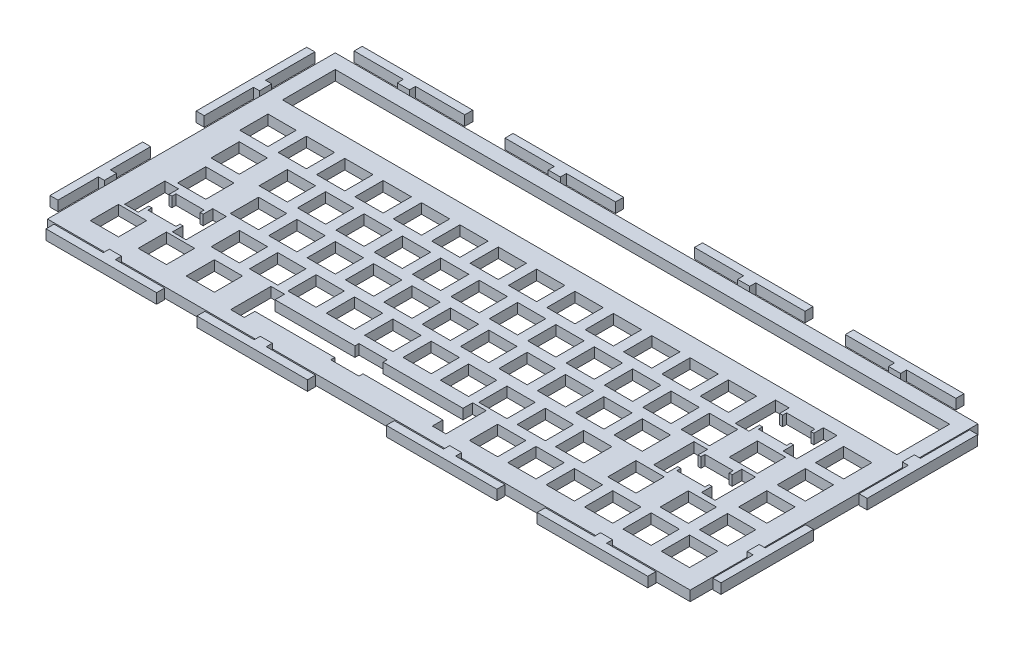
SolidWorks part; units mm, degrees
ref_plane "Front Plane" through (0, 0, 0) normal (0, 0, 1) x (1, 0, 0)
ref_plane "Top Plane" through (0, 0, 0) normal (0, 1, 0) x (1, 0, 0)
ref_plane "Right Plane" through (0, 0, 0) normal (1, 0, 0) x (0, 0, -1)
sketch "Sketch1" plane through (0, 0, 0) normal (0, 1, 0) x (1, 0, 0)
  line L2 (-75.7545, 37.9956) -> (-61.7545, 37.9956)
  line L3 (-94.8265, 37.9956) -> (-80.8265, 37.9956)
  line L4 (-94.8265, 37.9956) -> (-94.8265, 51.9956)
  line L5 (-94.8265, 51.9956) -> (-80.8265, 51.9956)
  line L6 (-80.8265, 37.9956) -> (-80.8265, 51.9956)
  line L7 (-75.7545, 37.9956) -> (-75.7545, 51.9956)
  line L8 (-75.7545, 51.9956) -> (-61.7545, 51.9956)
  line L9 (-61.7545, 37.9956) -> (-61.7545, 51.9956)
  line L10 (133.7495, 37.9956) -> (147.7495, 37.9956)
  line L11 (-37.6545, 37.9956) -> (-23.6545, 37.9956)
  line L12 (-56.7045, 37.9956) -> (-42.7045, 37.9956)
  line L13 (-56.7045, 37.9956) -> (-56.7045, 51.9956)
  line L14 (-56.7045, 51.9956) -> (-42.7045, 51.9956)
  line L15 (-42.7045, 37.9956) -> (-42.7045, 51.9956)
  line L16 (-37.6545, 37.9956) -> (-37.6545, 51.9956)
  line L17 (-37.6545, 51.9956) -> (-23.6545, 51.9956)
  line L18 (-23.6545, 37.9956) -> (-23.6545, 51.9956)
  line L19 (133.7495, 37.9956) -> (133.7495, 51.9956)
  line L20 (133.7495, 51.9956) -> (147.7495, 51.9956)
  line L21 (0.4455, 37.9956) -> (14.4455, 37.9956)
  line L22 (-18.6045, 37.9956) -> (-4.6045, 37.9956)
  line L23 (-18.6045, 37.9956) -> (-18.6045, 51.9956)
  line L24 (-18.6045, 51.9956) -> (-4.6045, 51.9956)
  line L25 (-4.6045, 37.9956) -> (-4.6045, 51.9956)
  line L26 (0.4455, 37.9956) -> (0.4455, 51.9956)
  line L27 (0.4455, 51.9956) -> (14.4455, 51.9956)
  line L28 (14.4455, 37.9956) -> (14.4455, 51.9956)
  line L29 (147.7495, 37.9956) -> (147.7495, 51.9956)
  line L30 (38.5455, 37.9956) -> (52.5455, 37.9956)
  line L31 (19.4955, 37.9956) -> (33.4955, 37.9956)
  line L32 (19.4955, 37.9956) -> (19.4955, 51.9956)
  line L33 (19.4955, 51.9956) -> (33.4955, 51.9956)
  line L34 (33.4955, 37.9956) -> (33.4955, 51.9956)
  line L35 (38.5455, 37.9956) -> (38.5455, 51.9956)
  line L36 (38.5455, 51.9956) -> (52.5455, 51.9956)
  line L37 (52.5455, 37.9956) -> (52.5455, 51.9956)
  line L38 (147.7495, 44.9956) -> (154.1495, 44.9956) construction
  line L39 (167.1835, 18.9456) -> (181.1835, 18.9456)
  line L40 (167.1835, 18.9456) -> (167.1835, 32.9456)
  line L41 (76.6455, 37.9956) -> (90.6455, 37.9956)
  line L42 (57.5955, 37.9956) -> (71.5955, 37.9956)
  line L43 (57.5955, 37.9956) -> (57.5955, 51.9956)
  line L44 (57.5955, 51.9956) -> (71.5955, 51.9956)
  line L45 (71.5955, 37.9956) -> (71.5955, 51.9956)
  line L46 (76.6455, 37.9956) -> (76.6455, 51.9956)
  line L47 (76.6455, 51.9956) -> (90.6455, 51.9956)
  line L48 (90.6455, 37.9956) -> (90.6455, 51.9956)
  line L49 (167.1835, 32.9456) -> (181.1835, 32.9456)
  line L50 (114.7225, 37.9956) -> (128.7225, 37.9956)
  line L51 (95.6955, 37.9956) -> (109.6955, 37.9956)
  line L52 (95.6955, 37.9956) -> (95.6955, 51.9956)
  line L53 (95.6955, 51.9956) -> (109.6955, 51.9956)
  line L54 (109.6955, 37.9956) -> (109.6955, 51.9956)
  line L55 (114.7225, 37.9956) -> (114.7225, 51.9956)
  line L56 (114.7225, 51.9956) -> (128.7225, 51.9956)
  line L57 (128.7225, 37.9956) -> (128.7225, 51.9956)
  line L58 (181.1835, 18.9456) -> (181.1835, 32.9456)
  line L59 (157.3735, 25.9456) -> (167.1835, 25.9456) construction
  line L73 (162.3995, 52.2456) -> (176.3995, 52.2456)
  line L75 (176.3995, 38.2456) -> (162.3995, 38.2456)
  line L77 (176.3995, 52.2456) -> (176.3995, 50.2456)
  line L78 (176.3995, 50.2456) -> (177.8995, 50.2456)
  line L79 (177.8995, 50.2456) -> (177.8995, 54.9956)
  line L80 (177.8995, 54.9956) -> (184.6495, 54.9956)
  line L81 (184.6495, 54.9956) -> (184.6495, 34.9956)
  line L82 (184.6495, 34.9956) -> (177.8995, 34.9956)
  line L83 (177.8995, 34.9956) -> (177.8995, 40.2456)
  line L84 (177.8995, 40.2456) -> (176.3995, 40.2456)
  line L85 (176.3995, 40.2456) -> (176.3995, 38.2456)
  line L86 (162.3995, 52.2456) -> (162.3995, 50.2456)
  line L87 (160.8995, 54.9956) -> (160.8995, 50.2456)
  line L88 (160.8995, 50.2456) -> (162.3995, 50.2456)
  line L89 (160.8995, 54.9956) -> (154.1495, 54.9956)
  line L90 (154.1495, 54.9956) -> (154.1495, 34.9956)
  line L91 (154.1495, 34.9956) -> (160.8995, 34.9956)
  line L92 (160.8995, 34.9956) -> (160.8995, 40.2456)
  line L93 (160.8995, 40.2456) -> (162.3995, 40.2456)
  line L94 (162.3995, 40.2456) -> (162.3995, 38.2456)
  line L116 (-47.1265, 18.9456) -> (-33.1265, 18.9456)
  line L117 (-66.1765, 18.9456) -> (-52.1765, 18.9456)
  line L118 (-66.1765, 18.9456) -> (-66.1765, 32.9456)
  line L119 (-66.1765, 32.9456) -> (-52.1765, 32.9456)
  line L120 (-52.1765, 18.9456) -> (-52.1765, 32.9456)
  line L121 (-47.1265, 18.9456) -> (-47.1265, 32.9456)
  line L122 (-47.1265, 32.9456) -> (-33.1265, 32.9456)
  line L123 (-33.1265, 18.9456) -> (-33.1265, 32.9456)
  line L125 (-9.0515, 18.9456) -> (4.9485, 18.9456)
  line L126 (-28.0765, 18.9456) -> (-14.0765, 18.9456)
  line L127 (-28.0765, 18.9456) -> (-28.0765, 32.9456)
  line L128 (-28.0765, 32.9456) -> (-14.0765, 32.9456)
  line L129 (-14.0765, 18.9456) -> (-14.0765, 32.9456)
  line L130 (-9.0515, 18.9456) -> (-9.0515, 32.9456)
  line L131 (-9.0515, 32.9456) -> (4.9485, 32.9456)
  line L132 (4.9485, 18.9456) -> (4.9485, 32.9456)
  line L135 (29.0735, 18.9456) -> (43.0735, 18.9456)
  line L136 (9.9485, 18.9456) -> (23.9485, 18.9456)
  line L137 (9.9485, 18.9456) -> (9.9485, 32.9456)
  line L138 (9.9485, 32.9456) -> (23.9485, 32.9456)
  line L139 (23.9485, 18.9456) -> (23.9485, 32.9456)
  line L140 (29.0735, 18.9456) -> (29.0735, 32.9456)
  line L141 (29.0735, 32.9456) -> (43.0735, 32.9456)
  line L142 (43.0735, 18.9456) -> (43.0735, 32.9456)
  line L144 (67.1485, 18.9456) -> (81.1485, 18.9456)
  line L145 (48.1235, 18.9456) -> (62.1235, 18.9456)
  line L146 (48.1235, 18.9456) -> (48.1235, 32.9456)
  line L147 (48.1235, 32.9456) -> (62.1235, 32.9456)
  line L148 (62.1235, 18.9456) -> (62.1235, 32.9456)
  line L149 (67.1485, 18.9456) -> (67.1485, 32.9456)
  line L150 (67.1485, 32.9456) -> (81.1485, 32.9456)
  line L151 (81.1485, 18.9456) -> (81.1485, 32.9456)
  line L152 (159.9865, 14.1456) -> (173.9865, 14.1456)
  line L153 (-42.3635, -0.1044) -> (-28.3635, -0.1044)
  line L154 (-61.4135, -0.1044) -> (-47.4135, -0.1044)
  line L155 (105.2735, 18.9456) -> (119.2735, 18.9456)
  line L156 (86.2235, 18.9456) -> (100.2235, 18.9456)
  line L157 (86.2235, 18.9456) -> (86.2235, 32.9456)
  line L158 (86.2235, 32.9456) -> (100.2235, 32.9456)
  line L159 (100.2235, 18.9456) -> (100.2235, 32.9456)
  line L160 (105.2735, 18.9456) -> (105.2735, 32.9456)
  line L161 (105.2735, 32.9456) -> (119.2735, 32.9456)
  line L162 (119.2735, 18.9456) -> (119.2735, 32.9456)
  line L163 (-61.4135, -0.1044) -> (-61.4135, 13.8956)
  line L172 (-94.8265, 37.9956) -> (-94.8265, 32.9456) construction
  line L173 (-61.4135, 13.8956) -> (-47.4135, 13.8956)
  line L174 (-47.4135, -0.1044) -> (-47.4135, 13.8956)
  line L175 (-90.0635, 18.9456) -> (-76.0635, 18.9456)
  line L176 (-90.0635, 18.9456) -> (-90.0635, 32.9456)
  line L177 (-90.0635, 32.9456) -> (-76.0635, 32.9456)
  line L178 (-76.0635, 18.9456) -> (-76.0635, 32.9456)
  line L179 (-94.8265, 32.9456) -> (-90.0635, 32.9456) construction
  line L180 (124.3235, 18.9456) -> (138.3235, 18.9456)
  line L185 (124.3235, 18.9456) -> (124.3235, 32.9456)
  line L186 (124.3235, 32.9456) -> (138.3235, 32.9456)
  line L187 (138.3235, 18.9456) -> (138.3235, 32.9456)
  line L188 (-42.3635, -0.1044) -> (-42.3635, 13.8956)
  line L189 (143.3735, 18.9456) -> (157.3735, 18.9456)
  line L190 (143.3735, 18.9456) -> (143.3735, 32.9456)
  line L191 (143.3735, 32.9456) -> (157.3735, 32.9456)
  line L192 (157.3735, 18.9456) -> (157.3735, 32.9456)
  line L193 (-42.3635, 13.8956) -> (-28.3635, 13.8956)
  line L194 (-28.3635, -0.1044) -> (-28.3635, 13.8956)
  line L195 (-4.2635, -0.1044) -> (9.7365, -0.1044)
  line L196 (-23.3135, -0.1044) -> (-9.3135, -0.1044)
  line L197 (-23.3135, -0.1044) -> (-23.3135, 13.8956)
  line L198 (-23.3135, 13.8956) -> (-9.3135, 13.8956)
  line L199 (-9.3135, -0.1044) -> (-9.3135, 13.8956)
  line L200 (-4.2635, -0.1044) -> (-4.2635, 13.8956)
  line L201 (-4.2635, 13.8956) -> (9.7365, 13.8956)
  line L202 (9.7365, -0.1044) -> (9.7365, 13.8956)
  line L203 (33.8365, -0.1044) -> (47.8365, -0.1044)
  line L204 (14.7865, -0.1044) -> (28.7865, -0.1044)
  line L205 (14.7865, -0.1044) -> (14.7865, 13.8956)
  line L206 (14.7865, 13.8956) -> (28.7865, 13.8956)
  line L207 (28.7865, -0.1044) -> (28.7865, 13.8956)
  line L208 (33.8365, -0.1044) -> (33.8365, 13.8956)
  line L209 (33.8365, 13.8956) -> (47.8365, 13.8956)
  line L210 (47.8365, -0.1044) -> (47.8365, 13.8956)
  line L211 (71.9365, -0.1044) -> (85.9365, -0.1044)
  line L212 (52.8865, -0.1044) -> (66.8865, -0.1044)
  line L213 (52.8865, -0.1044) -> (52.8865, 13.8956)
  line L214 (52.8865, 13.8956) -> (66.8865, 13.8956)
  line L215 (66.8865, -0.1044) -> (66.8865, 13.8956)
  line L216 (71.9365, -0.1044) -> (71.9365, 13.8956)
  line L217 (71.9365, 13.8956) -> (85.9365, 13.8956)
  line L218 (85.9365, -0.1044) -> (85.9365, 13.8956)
  line L219 (110.0365, -0.1044) -> (124.0365, -0.1044)
  line L220 (90.9865, -0.1044) -> (104.9865, -0.1044)
  line L221 (90.9865, -0.1044) -> (90.9865, 13.8956)
  line L222 (90.9865, 13.8956) -> (104.9865, 13.8956)
  line L223 (104.9865, -0.1044) -> (104.9865, 13.8956)
  line L224 (110.0365, -0.1044) -> (110.0365, 13.8956)
  line L225 (110.0365, 13.8956) -> (124.0365, 13.8956)
  line L226 (124.0365, -0.1044) -> (124.0365, 13.8956)
  line L227 (-87.6075, -0.1044) -> (-73.6075, -0.1044)
  line L228 (-87.6075, -0.1044) -> (-87.6075, 13.8956)
  line L229 (-87.6075, 13.8956) -> (-73.6075, 13.8956)
  line L230 (-73.6075, -0.1044) -> (-73.6075, 13.8956)
  line L231 (-90.0635, 18.9456) -> (-90.0635, 13.8956) construction
  line L232 (129.0865, -0.1044) -> (143.0865, -0.1044)
  line L233 (129.0865, -0.1044) -> (129.0865, 13.8956)
  line L234 (129.0865, 13.8956) -> (143.0865, 13.8956)
  line L235 (143.0865, -0.1044) -> (143.0865, 13.8956)
  line L240 (-90.0635, 13.8956) -> (-87.6075, 13.8956) construction
  line L241 (173.9865, 0.1456) -> (159.9865, 0.1456)
  line L242 (173.9865, 14.1456) -> (173.9865, 12.1456)
  line L243 (173.9865, 12.1456) -> (175.4865, 12.1456)
  line L244 (175.4865, 12.1456) -> (175.4865, 16.8956)
  line L245 (175.4865, 16.8956) -> (182.2365, 16.8956)
  line L246 (182.2365, 16.8956) -> (182.2365, -3.1044)
  line L247 (182.2365, -3.1044) -> (175.4865, -3.1044)
  line L248 (175.4865, -3.1044) -> (175.4865, 2.1456)
  line L249 (175.4865, 2.1456) -> (173.9865, 2.1456)
  line L250 (173.9865, 2.1456) -> (173.9865, 0.1456)
  line L251 (159.9865, 14.1456) -> (159.9865, 12.1456)
  line L252 (158.4865, 16.8956) -> (158.4865, 12.1456)
  line L253 (158.4865, 12.1456) -> (159.9865, 12.1456)
  line L254 (158.4865, 16.8956) -> (151.7365, 16.8956)
  line L255 (151.7365, 16.8956) -> (151.7365, -3.1044)
  line L256 (151.7365, -3.1044) -> (158.4865, -3.1044)
  line L257 (158.4865, -3.1044) -> (158.4865, 2.1456)
  line L258 (158.4865, 2.1456) -> (159.9865, 2.1456)
  line L259 (159.9865, 2.1456) -> (159.9865, 0.1456)
  line L260 (143.0865, 12.1456) -> (151.7365, 12.1456) construction
  line L262 (-32.8385, -19.1544) -> (-18.8385, -19.1544)
  line L263 (-51.8885, -19.1544) -> (-37.8885, -19.1544)
  line L264 (-51.8885, -19.1544) -> (-51.8885, -5.1544)
  line L265 (-51.8885, -5.1544) -> (-37.8885, -5.1544)
  line L266 (-37.8885, -19.1544) -> (-37.8885, -5.1544)
  line L267 (-32.8385, -19.1544) -> (-32.8385, -5.1544)
  line L268 (-32.8385, -5.1544) -> (-18.8385, -5.1544)
  line L269 (-18.8385, -19.1544) -> (-18.8385, -5.1544)
  line L270 (5.2615, -19.1544) -> (19.2615, -19.1544)
  line L271 (-13.7885, -19.1544) -> (0.2115, -19.1544)
  line L272 (-13.7885, -19.1544) -> (-13.7885, -5.1544)
  line L273 (-13.7885, -5.1544) -> (0.2115, -5.1544)
  line L274 (0.2115, -19.1544) -> (0.2115, -5.1544)
  line L275 (5.2615, -19.1544) -> (5.2615, -5.1544)
  line L276 (5.2615, -5.1544) -> (19.2615, -5.1544)
  line L277 (19.2615, -19.1544) -> (19.2615, -5.1544)
  line L278 (43.3615, -19.1544) -> (57.3615, -19.1544)
  line L279 (24.3115, -19.1544) -> (38.3115, -19.1544)
  line L280 (24.3115, -19.1544) -> (24.3115, -5.1544)
  line L281 (24.3115, -5.1544) -> (38.3115, -5.1544)
  line L282 (38.3115, -19.1544) -> (38.3115, -5.1544)
  line L283 (43.3615, -19.1544) -> (43.3615, -5.1544)
  line L284 (43.3615, -5.1544) -> (57.3615, -5.1544)
  line L285 (57.3615, -19.1544) -> (57.3615, -5.1544)
  line L286 (81.4615, -19.6544) -> (95.4615, -19.6544)
  line L287 (62.4115, -19.6544) -> (76.4115, -19.6544)
  line L288 (62.4115, -19.6544) -> (62.4115, -5.6544)
  line L289 (62.4115, -5.6544) -> (76.4115, -5.6544)
  line L290 (76.4115, -19.6544) -> (76.4115, -5.6544)
  line L291 (81.4615, -19.6544) -> (81.4615, -5.6544)
  line L292 (81.4615, -5.6544) -> (95.4615, -5.6544)
  line L293 (95.4615, -19.6544) -> (95.4615, -5.6544)
  line L294 (119.5615, -19.6544) -> (133.5615, -19.6544)
  line L295 (100.5115, -19.6544) -> (114.5115, -19.6544)
  line L296 (100.5115, -19.6544) -> (100.5115, -5.6544)
  line L297 (100.5115, -5.6544) -> (114.5115, -5.6544)
  line L298 (114.5115, -19.6544) -> (114.5115, -5.6544)
  line L299 (119.5615, -19.6544) -> (119.5615, -5.6544)
  line L300 (119.5615, -5.6544) -> (133.5615, -5.6544)
  line L301 (133.5615, -19.6544) -> (133.5615, -5.6544)
  line L306 (-83.3445, -5.1544) -> (-69.3445, -5.1544)
  line L307 (145.5235, -19.6544) -> (159.5235, -19.6544)
  line L308 (145.5235, -19.6544) -> (145.5235, -5.6544)
  line L309 (145.5235, -5.6544) -> (159.5235, -5.6544)
  line L310 (159.5235, -19.6544) -> (159.5235, -5.6544)
  line L311 (-69.3445, -19.1544) -> (-83.3445, -19.1544)
  line L331 (171.4855, -19.6544) -> (185.4855, -19.6544)
  line L332 (171.4855, -19.6544) -> (171.4855, -5.6544)
  line L333 (171.4855, -5.6544) -> (185.4855, -5.6544)
  line L334 (185.4855, -19.6544) -> (185.4855, -5.6544)
  line L335 (159.5235, -12.6544) -> (171.4855, -12.6544) construction
  line L336 (-61.4135, -0.1044) -> (-61.4135, -5.1544) construction
  line L337 (-61.4135, -5.1544) -> (-51.8885, -5.1544) construction
  line L338 (-104.4215, 94.9896) -> (-117.5239, 94.9896) construction
  line L339 (-97.2765, 61.6456) -> (207.7235, 61.6456)
  line L340 (190.9955, 18.9456) -> (204.9955, 18.9456)
  line L341 (190.9955, 18.9456) -> (190.9955, 32.9456)
  line L342 (190.9955, 32.9456) -> (204.9955, 32.9456)
  line L343 (204.9955, 18.9456) -> (204.9955, 32.9456)
  line L344 (181.1835, 25.9456) -> (190.9955, 25.9456) construction
  line L345 (190.9745, 37.9956) -> (204.9745, 37.9956)
  line L346 (190.9745, 37.9956) -> (190.9745, 51.9956)
  line L347 (190.9745, 51.9956) -> (204.9745, 51.9956)
  line L348 (204.9745, 37.9956) -> (204.9745, 51.9956)
  line L349 (184.6495, 44.9956) -> (190.9745, 44.9956) construction
  line L350 (190.9425, -0.1044) -> (204.9425, -0.1044)
  line L351 (190.9425, -0.1044) -> (190.9425, 13.8956)
  line L352 (190.9425, 13.8956) -> (204.9425, 13.8956)
  line L353 (204.9425, -0.1044) -> (204.9425, 13.8956)
  line L354 (182.2365, 6.8956) -> (190.9425, 6.8956) construction
  line L355 (190.9855, -19.6544) -> (204.9855, -19.6544)
  line L356 (190.9855, -19.6544) -> (190.9855, -5.6544)
  line L357 (190.9855, -5.6544) -> (204.9855, -5.6544)
  line L358 (204.9855, -19.6544) -> (204.9855, -5.6544)
  line L359 (185.4855, -12.6544) -> (190.9855, -12.6544) construction
  line L360 (-69.3445, -5.1544) -> (-69.3445, -7.1544)
  line L361 (-69.3445, -7.1544) -> (-67.8445, -7.1544)
  line L362 (-67.8445, -7.1544) -> (-67.8445, -2.4044)
  line L363 (-67.8445, -2.4044) -> (-61.0945, -2.4044)
  line L364 (-61.0945, -2.4044) -> (-61.0945, -22.4044)
  line L365 (-61.0945, -22.4044) -> (-67.8445, -22.4044)
  line L366 (-67.8445, -22.4044) -> (-67.8445, -17.1544)
  line L367 (-67.8445, -17.1544) -> (-69.3445, -17.1544)
  line L368 (-69.3445, -17.1544) -> (-69.3445, -19.1544)
  line L369 (-83.3445, -5.1544) -> (-83.3445, -7.1544)
  line L370 (-84.8445, -2.4044) -> (-84.8445, -7.1544)
  line L371 (-84.8445, -7.1544) -> (-83.3445, -7.1544)
  line L372 (-84.8445, -2.4044) -> (-91.5945, -2.4044)
  line L373 (-91.5945, -2.4044) -> (-91.5945, -22.4044)
  line L374 (-91.5945, -22.4044) -> (-84.8445, -22.4044)
  line L375 (-84.8445, -22.4044) -> (-84.8445, -17.1544)
  line L376 (-84.8445, -17.1544) -> (-83.3445, -17.1544)
  line L377 (-83.3445, -17.1544) -> (-83.3445, -19.1544)
  line L378 (-93.0945, -37.9544) -> (-79.0945, -37.9544)
  line L379 (-93.0945, -37.9544) -> (-93.0945, -23.9544)
  line L380 (-93.0945, -23.9544) -> (-79.0945, -23.9544)
  line L381 (-79.0945, -37.9544) -> (-79.0945, -23.9544)
  line L382 (-69.2945, -37.9544) -> (-55.2945, -37.9544)
  line L383 (-69.2945, -37.9544) -> (-69.2945, -23.9544)
  line L384 (-69.2945, -23.9544) -> (-55.2945, -23.9544)
  line L385 (-55.2945, -37.9544) -> (-55.2945, -23.9544)
  line L390 (-45.4945, -37.9544) -> (-31.4945, -37.9544)
  line L391 (-45.4945, -37.9544) -> (-45.4945, -23.9544)
  line L392 (-45.4945, -23.9544) -> (-31.4945, -23.9544)
  line L393 (-31.4945, -37.9544) -> (-31.4945, -23.9544)
  line L394 (-55.2945, -23.9544) -> (-45.4945, -23.9544) construction
  line L395 (26.4395, -24.1144) -> (40.4395, -24.1144)
  line L396 (40.4395, -38.1144) -> (26.4395, -38.1144)
  line L397 (40.4395, -24.1144) -> (40.4395, -26.1144)
  line L398 (40.4395, -26.1144) -> (80.1235, -26.1144)
  line L399 (80.1235, -26.1144) -> (80.1235, -21.3644)
  line L400 (80.1235, -21.3644) -> (86.8735, -21.3644)
  line L401 (86.8735, -21.3644) -> (86.8735, -41.3644)
  line L402 (86.8735, -41.3644) -> (80.1235, -41.3644)
  line L403 (80.1235, -41.3644) -> (80.1235, -36.1144)
  line L404 (80.1235, -36.1144) -> (40.4395, -36.1144)
  line L405 (40.4395, -36.1144) -> (40.4395, -38.1144)
  line L406 (26.4395, -24.1144) -> (26.4395, -26.1144)
  line L407 (-13.2445, -21.3644) -> (-13.2445, -26.1144)
  line L408 (-13.2445, -26.1144) -> (26.4395, -26.1144)
  line L409 (-13.2445, -21.3644) -> (-19.9945, -21.3644)
  line L410 (-19.9945, -21.3644) -> (-19.9945, -41.3644)
  line L411 (-19.9945, -41.3644) -> (-13.2445, -41.3644)
  line L412 (-13.2445, -41.3644) -> (-13.2445, -36.1144)
  line L413 (-13.2445, -36.1144) -> (26.4395, -36.1144)
  line L414 (26.4395, -36.1144) -> (26.4395, -38.1144)
  line L415 (95.5435, -38.3644) -> (109.5435, -38.3644)
  line L416 (95.5435, -38.3644) -> (95.5435, -24.3644)
  line L417 (95.5435, -24.3644) -> (109.5435, -24.3644)
  line L418 (109.5435, -38.3644) -> (109.5435, -24.3644)
  line L419 (86.8735, -31.3644) -> (95.5435, -31.3644) construction
  line L420 (114.5935, -38.3644) -> (128.5935, -38.3644)
  line L421 (114.5935, -38.3644) -> (114.5935, -24.3644)
  line L422 (114.5935, -24.3644) -> (128.5935, -24.3644)
  line L423 (128.5935, -38.3644) -> (128.5935, -24.3644)
  line L424 (114.5935, -31.3644) -> (109.5435, -31.3644) construction
  line L425 (133.6435, -38.3644) -> (147.6435, -38.3644)
  line L426 (133.6435, -38.3644) -> (133.6435, -24.3644)
  line L427 (133.6435, -24.3644) -> (147.6435, -24.3644)
  line L428 (147.6435, -38.3644) -> (147.6435, -24.3644)
  line L429 (152.6935, -38.3644) -> (166.6935, -38.3644)
  line L430 (152.6935, -38.3644) -> (152.6935, -24.3644)
  line L431 (152.6935, -24.3644) -> (166.6935, -24.3644)
  line L432 (166.6935, -38.3644) -> (166.6935, -24.3644)
  line L433 (171.7435, -38.3644) -> (185.7435, -38.3644)
  line L434 (171.7435, -38.3644) -> (171.7435, -24.3644)
  line L435 (171.7435, -24.3644) -> (185.7435, -24.3644)
  line L436 (185.7435, -38.3644) -> (185.7435, -24.3644)
  line L437 (190.7935, -38.3644) -> (204.7935, -38.3644)
  line L438 (190.7935, -38.3644) -> (190.7935, -24.3644)
  line L439 (190.7935, -24.3644) -> (204.7935, -24.3644)
  line L440 (204.7935, -38.3644) -> (204.7935, -24.3644)
  line L441 (-97.2765, 61.6456) -> (-97.2765, 87.8456)
  line L442 (-97.2765, 87.8456) -> (207.7235, 87.8456)
  line L443 (207.7235, 61.6456) -> (207.7235, 87.8456)
  line L444 (-104.4215, 94.9896) -> (214.6585, 94.9896)
  line L445 (-104.4215, 94.9896) -> (-104.4215, -47.8854)
  line L446 (-104.4215, -47.8854) -> (214.6585, -47.8854)
  line L447 (214.6585, 94.9896) -> (214.6585, -47.8854)
  line L448 (-117.5239, 94.9896) -> (-117.5239, 25.8096) construction
  line L449 (-104.4215, -47.8854) -> (-117.5239, -47.8854) construction
  line L450 (-117.5239, -47.8854) -> (-117.5239, 14.6046) construction
  line L451 (-150.5498, 25.8096) -> (-98.6233, 25.8096) construction
  line L452 (-150.5498, 14.6046) -> (-97.2765, 14.6046) construction
  line L453 (-104.4215, 94.9896) -> (-104.4215, 60.3996) construction
  point P115 (128.7225, 44.9956)
  point P116 (154.1495, 44.9956)
  dimension "D1" = 14
  dimension "D2" = 20
  dimension "D3" = 4.75
  dimension "D4" = 6.75
  dimension "D5" = 1.5
  dimension "D6" = 2
  dimension "D13" = 14
  dimension "D14" = 14
  dimension "D15" = 5.072
  dimension "D16" = 14
  dimension "D17" = 5.05
  dimension "D18" = 5.05
  dimension "D19" = 14
  dimension "D20" = 4.763
  dimension "D21" = 5.05
  dimension "D22" = 9.887
  dimension "D23" = 26.2
  dimension "D24" = 14
  dimension "D25" = 14
  dimension "D26" = 5.05
  dimension "D27" = 5.05
  dimension "D28" = 5.05
  dimension "D29" = 5.05
  dimension "D30" = 5.05
  dimension "D31" = 5.05
  dimension "D32" = 5.05
  dimension "D33" = 5.05
  dimension "D34" = 5.05
  dimension "D35" = 5.027
  dimension "D36" = 5.05
  dimension "D37" = 5.05
  dimension "D38" = 5.025
  dimension "D39" = 5
  dimension "D40" = 5.125
  dimension "D41" = 5.05
  dimension "D42" = 5.025
  dimension "D43" = 5.075
  dimension "D44" = 5.05
  dimension "D45" = 5.05
  dimension "D46" = 5.027
  dimension "D47" = 14.65
  dimension "D48" = 14
  dimension "D49" = 9.81
  dimension "D50" = 12.194
  dimension "D51" = 5.05
  dimension "D52" = 5.05
  dimension "D53" = 5.05
  dimension "D54" = 5.05
  dimension "D55" = 5.05
  dimension "D56" = 5.05
  dimension "D57" = 5.05
  dimension "D58" = 5.05
  dimension "D59" = 5.05
  dimension "D60" = 5.05
  dimension "D61" = 14
  dimension "D62" = 20
  dimension "D63" = 5.05
  dimension "D64" = 2.456
  dimension "D65" = 4.75
  dimension "D66" = 6.75
  dimension "D67" = 1.5
  dimension "D68" = 2
  dimension "D69" = 16.9
  dimension "D70" = 14
  dimension "D71" = 5.05
  dimension "D72" = 5.05
  dimension "D73" = 5.05
  dimension "D74" = 5.05
  dimension "D75" = 5.05
  dimension "D76" = 5.05
  dimension "D77" = 5.05
  dimension "D78" = 5.05
  dimension "D79" = 5.05
  dimension "D80" = 11.962
  dimension "D81" = 20
  dimension "D82" = 14
  dimension "D83" = 11.962
  dimension "D84" = 14
  dimension "D85" = 14
  dimension "D86" = 9.812
  dimension "D87" = 14
  dimension "D88" = 14.575
  dimension "D89" = 4.75
  dimension "D90" = 14
  dimension "D91" = 6.75
  dimension "D92" = 14
  dimension "D93" = 16.956
  dimension "D94" = 14
  dimension "D95" = 5.5
  dimension "D96" = 5.05
  dimension "D97" = 5.05
  dimension "D98" = 9.525
  dimension "D99" = 1.5
  dimension "D100" = 2
  dimension "D101" = 5.05
  dimension "D102" = 9.206
  dimension "D103" = 5.05
  dimension "D104" = 14
  dimension "D105" = 14
  dimension "D106" = 14
  dimension "D107" = 14
  dimension "D108" = 1.5
  dimension "D109" = 9.8
  dimension "D110" = 5.05
  dimension "D111" = 9.8
  dimension "D112" = 5.05
  dimension "D113" = 5.05
  dimension "D114" = 14
  dimension "D115" = 14
  dimension "D116" = 20
  dimension "D117" = 4.75
  dimension "D118" = 6.75
  dimension "D119" = 39.684
  dimension "D120" = 2
  dimension "D121" = 5.05
  dimension "D122" = 11.5
  dimension "D123" = 14
  dimension "D124" = 8.67
  dimension "D125" = 5.25
  dimension "D126" = 14
  dimension "D127" = 5.05
  dimension "D128" = 14
  dimension "D129" = 14
  dimension "D130" = 14
  dimension "D131" = 14
  dimension "D132" = 5.05
  dimension "D133" = 5.05
  dimension "D134" = 5.05
  dimension "D135" = 5.05
  dimension "D136" = 4.8
  dimension "D137" = 5.25
  dimension "D138" = 5.25
  dimension "D139" = 5.25
  dimension "D140" = 305
  dimension "D141" = 9.65
  dimension "D142" = 142.875
  dimension "D143" = 319.08
  dimension "D144" = 7.144
  dimension "D145" = 7.145
  dimension "D146" = 2.45
  dimension "D147" = 69.18
  dimension "D148" = 62.49
extrude "Boss-Extrude2" add sketch "Sketch1" along normal mid plane 5
sketch "Sketch2" plane through (0, 2.5, 0) normal (0, 1, 0) x (1, 0, 0)
  line L0 (-104.4215, 25.7896) -> (-104.4215, 14.6146) construction
  line L1 (-104.4215, -47.8854) -> (-104.4215, 14.6146) construction
  line L2 (-104.4215, 94.9896) -> (-104.4215, -47.8854) construction
  line L3 (-104.4215, 94.9896) -> (-104.4215, 25.7896) construction
  line L4 (-104.4215, 60.3896) -> (-192.4203, 60.3896) construction
  line L5 (-104.4215, 63.3896) -> (-104.4215, 57.3896)
  line L6 (-104.4215, 63.3896) -> (-107.4215, 63.3896)
  line L7 (-104.4215, 57.3896) -> (-107.4215, 57.3896)
  line L8 (-107.4215, 63.3896) -> (-107.4215, 87.8456)
  line L9 (-107.4215, 57.3896) -> (-107.4215, 32.9456)
  line L10 (-107.4215, 87.8456) -> (-111.4215, 87.8456)
  line L11 (-111.4215, 87.8456) -> (-111.4215, 32.9456)
  line L12 (-111.4215, 32.9456) -> (-107.4215, 32.9456)
  line L13 (207.7235, 87.8456) -> (-97.2765, 87.8456) construction
  line L14 (-107.4215, 20.2021) -> (-104.4215, 20.2021) construction
  line L15 (-76.0635, 32.9456) -> (-90.0635, 32.9456) construction
  line L16 (-107.4215, 31.2421) -> (-107.4215, 9.1621) construction
  line L17 (-104.4215, -13.6354) -> (-104.4215, -19.6354)
  line L18 (-104.4215, -13.6354) -> (-107.4215, -13.6354)
  line L19 (-104.4215, -19.6354) -> (-107.4215, -19.6354)
  line L20 (-107.4215, -13.6354) -> (-107.4215, 6.3646)
  line L21 (-107.4215, 6.3646) -> (-111.4215, 6.3646)
  line L22 (-111.4215, 6.3646) -> (-111.4215, -39.6354)
  line L23 (-111.4215, -39.6354) -> (-107.4215, -39.6354)
  line L24 (-107.4215, -39.6354) -> (-107.4215, -19.6354)
  line L25 (214.6585, 14.5646) -> (214.6585, -47.8854) construction
  line L26 (55.1185, 125.0696) -> (55.1185, -78.0627) construction
  line L27 (221.6585, -39.6354) -> (217.6585, -39.6354)
  line L28 (221.6585, 6.3646) -> (221.6585, -39.6354)
  line L29 (217.6585, 6.3646) -> (221.6585, 6.3646)
  line L30 (217.6585, -13.6354) -> (217.6585, 6.3646)
  line L31 (214.6585, -13.6354) -> (217.6585, -13.6354)
  line L32 (214.6585, -13.6354) -> (214.6585, -19.6354)
  line L33 (214.6585, -19.6354) -> (217.6585, -19.6354)
  line L34 (217.6585, -39.6354) -> (217.6585, -19.6354)
  line L35 (214.6585, 63.3896) -> (217.6585, 63.3896)
  line L36 (217.6585, 63.3896) -> (217.6585, 87.8456)
  line L37 (217.6585, 87.8456) -> (221.6585, 87.8456)
  line L38 (221.6585, 87.8456) -> (221.6585, 32.9456)
  line L39 (221.6585, 32.9456) -> (217.6585, 32.9456)
  line L40 (217.6585, 57.3896) -> (217.6585, 32.9456)
  line L41 (214.6585, 57.3896) -> (217.6585, 57.3896)
  line L42 (214.6585, 63.3896) -> (214.6585, 57.3896)
  line L43 (214.6585, -47.8854) -> (214.6585, 94.9896) construction
  line L44 (214.6585, 94.9896) -> (214.6585, 25.7896) construction
  line L45 (214.6585, 25.7896) -> (214.6585, 14.5646) construction
  line L46 (214.6585, 20.1771) -> (217.6585, 20.1771) construction
  line L47 (217.6585, 31.2421) -> (217.6585, 9.1621) construction
  line L48 (55.1185, 94.9896) -> (55.1185, -47.8854) construction
  line L49 (214.6585, 94.9896) -> (-104.4215, 94.9896) construction
  line L50 (-104.4215, -47.8854) -> (214.6585, -47.8854) construction
  line L51 (55.1185, 23.5034) -> (270.1989, 23.5034) construction
  line L52 (55.1185, 23.5034) -> (-168.679, 23.5034) construction
  line L53 (214.6585, 94.9896) -> (56.9085, 94.9896) construction
  line L54 (-104.4215, 94.9896) -> (45.7235, 94.9896) construction
  line L55 (45.7235, 94.9896) -> (56.9085, 94.9896) construction
  line L56 (51.316, 94.9896) -> (51.316, 98.9896) construction
  line L57 (40.276, 98.9896) -> (62.356, 98.9896) construction
  line L58 (170.2335, 94.9896) -> (176.2335, 94.9896)
  line L59 (176.2335, 94.9896) -> (176.2335, 97.9896)
  line L60 (176.2335, 97.9896) -> (200.6835, 97.9896)
  line L61 (200.6835, 97.9896) -> (200.6835, 101.9896)
  line L62 (200.6835, 101.9896) -> (145.7835, 101.9896)
  line L63 (145.7835, 101.9896) -> (145.7835, 97.9896)
  line L64 (145.7835, 97.9896) -> (170.2335, 97.9896)
  line L65 (170.2335, 97.9896) -> (170.2335, 94.9896)
  line L66 (95.3335, 94.9896) -> (101.3335, 94.9896)
  line L67 (101.3335, 94.9896) -> (101.3335, 97.9896)
  line L68 (101.3335, 97.9896) -> (125.7835, 97.9896)
  line L69 (125.7835, 97.9896) -> (125.7835, 101.9896)
  line L70 (125.7835, 101.9896) -> (70.8835, 101.9896)
  line L71 (70.8835, 101.9896) -> (70.8835, 97.9896)
  line L72 (70.8835, 97.9896) -> (95.3335, 97.9896)
  line L73 (95.3335, 97.9896) -> (95.3335, 94.9896)
  line L74 (125.7835, 99.9896) -> (145.7835, 99.9896) construction
  line L75 (135.7835, 94.9896) -> (135.7835, 104.9896) construction
  line L76 (-43.1515, 97.9896) -> (-67.6015, 97.9896)
  line L77 (-43.1515, 101.9896) -> (-43.1515, 97.9896)
  line L78 (-98.0515, 101.9896) -> (-43.1515, 101.9896)
  line L79 (-98.0515, 97.9896) -> (-98.0515, 101.9896)
  line L80 (-73.6015, 97.9896) -> (-98.0515, 97.9896)
  line L81 (-73.6015, 94.9896) -> (-73.6015, 97.9896)
  line L82 (-67.6015, 94.9896) -> (-73.6015, 94.9896)
  line L83 (-67.6015, 97.9896) -> (-67.6015, 94.9896)
  line L84 (7.2985, 97.9896) -> (7.2985, 94.9896)
  line L85 (31.7485, 97.9896) -> (7.2985, 97.9896)
  line L86 (31.7485, 101.9896) -> (31.7485, 97.9896)
  line L87 (-23.1515, 101.9896) -> (31.7485, 101.9896)
  line L88 (-23.1515, 97.9896) -> (-23.1515, 101.9896)
  line L89 (1.2985, 97.9896) -> (-23.1515, 97.9896)
  line L90 (1.2985, 94.9896) -> (1.2985, 97.9896)
  line L91 (7.2985, 94.9896) -> (1.2985, 94.9896)
  line L92 (145.7835, -50.9827) -> (170.2335, -50.9827)
  line L93 (145.7835, -54.9827) -> (145.7835, -50.9827)
  line L94 (200.6835, -54.9827) -> (145.7835, -54.9827)
  line L95 (200.6835, -50.9827) -> (200.6835, -54.9827)
  line L96 (176.2335, -50.9827) -> (200.6835, -50.9827)
  line L97 (176.2335, -47.9827) -> (176.2335, -50.9827)
  line L98 (170.2335, -47.9827) -> (176.2335, -47.9827)
  line L99 (170.2335, -50.9827) -> (170.2335, -47.9827)
  line L100 (95.3335, -50.9827) -> (95.3335, -47.9827)
  line L101 (70.8835, -50.9827) -> (95.3335, -50.9827)
  line L102 (70.8835, -54.9827) -> (70.8835, -50.9827)
  line L103 (125.7835, -54.9827) -> (70.8835, -54.9827)
  line L104 (125.7835, -50.9827) -> (125.7835, -54.9827)
  line L105 (101.3335, -50.9827) -> (125.7835, -50.9827)
  line L106 (101.3335, -47.9827) -> (101.3335, -50.9827)
  line L107 (95.3335, -47.9827) -> (101.3335, -47.9827)
  line L108 (31.7485, -50.9827) -> (7.2985, -50.9827)
  line L109 (31.7485, -54.9827) -> (31.7485, -50.9827)
  line L110 (-23.1515, -54.9827) -> (31.7485, -54.9827)
  line L111 (-23.1515, -50.9827) -> (-23.1515, -54.9827)
  line L112 (1.2985, -50.9827) -> (-23.1515, -50.9827)
  line L113 (1.2985, -47.9827) -> (1.2985, -50.9827)
  line L114 (7.2985, -47.9827) -> (1.2985, -47.9827)
  line L115 (7.2985, -50.9827) -> (7.2985, -47.9827)
  line L116 (-43.1515, -54.9827) -> (-43.1515, -50.9827)
  line L117 (-98.0515, -54.9827) -> (-43.1515, -54.9827)
  line L118 (-98.0515, -50.9827) -> (-98.0515, -54.9827)
  line L119 (-73.6015, -50.9827) -> (-98.0515, -50.9827)
  line L120 (-73.6015, -47.9827) -> (-73.6015, -50.9827)
  line L121 (-67.6015, -47.9827) -> (-73.6015, -47.9827)
  line L122 (-67.6015, -50.9827) -> (-67.6015, -47.9827)
  line L123 (-43.1515, -50.9827) -> (-67.6015, -50.9827)
  line L124 (214.6585, -47.8854) -> (56.9135, -47.8854) construction
  line L125 (-104.4215, 94.9896) -> (-104.4215, 96.9896) construction
  line L126 (-104.4215, -47.8854) -> (45.7225, -47.8854) construction
  line L127 (45.7225, -47.8854) -> (56.9135, -47.8854) construction
  line L128 (51.318, -47.8854) -> (51.318, -52.8854) construction
  line L129 (40.276, -52.8854) -> (62.356, -52.8854) construction
  line L130 (-104.4215, 96.9896) -> (-90.2825, 96.9896) construction
  line L131 (-90.2825, 96.9896) -> (-81.3425, 96.9896) construction
  point P17 (-104.4215, 60.3896)
  point P21 (-104.4215, 60.3896)
  point P28 (-104.4215, 20.2021)
  point P31 (-104.4215, -16.6354)
  point P34 (-104.4215, -16.6354)
  point P84 (51.316, 98.9896)
  point P103 (145.7835, 99.9896)
  point P106 (135.7835, 99.9896)
  point P107 (135.7835, 99.9896)
  dimension "D1" = 69.2
  dimension "D2" = 62.5
  dimension "D3" = 3
  dimension "D4" = 6
  dimension "D5" = 0
  dimension "D6" = 0
  dimension "D7" = 22.08
  dimension "D8" = 3
  dimension "D9" = 6
  dimension "D10" = 3
  dimension "D11" = 20
  dimension "D12" = 4
  dimension "D13" = 4
  dimension "D14" = 62.45
  dimension "D15" = 69.2
  dimension "D16" = 22.08
  dimension "D17" = 157.75
  dimension "D18" = 150.145
  dimension "D19" = 4
  dimension "D20" = 22.08
  dimension "D21" = 6
  dimension "D22" = 3
  dimension "D23" = 4
  dimension "D24" = 54.9
  dimension "D25" = 6
  dimension "D26" = 3
  dimension "D27" = 4
  dimension "D28" = 54.9
  dimension "D29" = 20
  dimension "D30" = 10
  dimension "D31" = 157.745
  dimension "D32" = 150.144
  dimension "D33" = 5
  dimension "D34" = 22.08
  dimension "D35" = 2
  dimension "D36" = 14.139
  dimension "D37" = 8.94
extrude "Boss-Extrude3" add sketch "Sketch2" along normal mid plane 5
